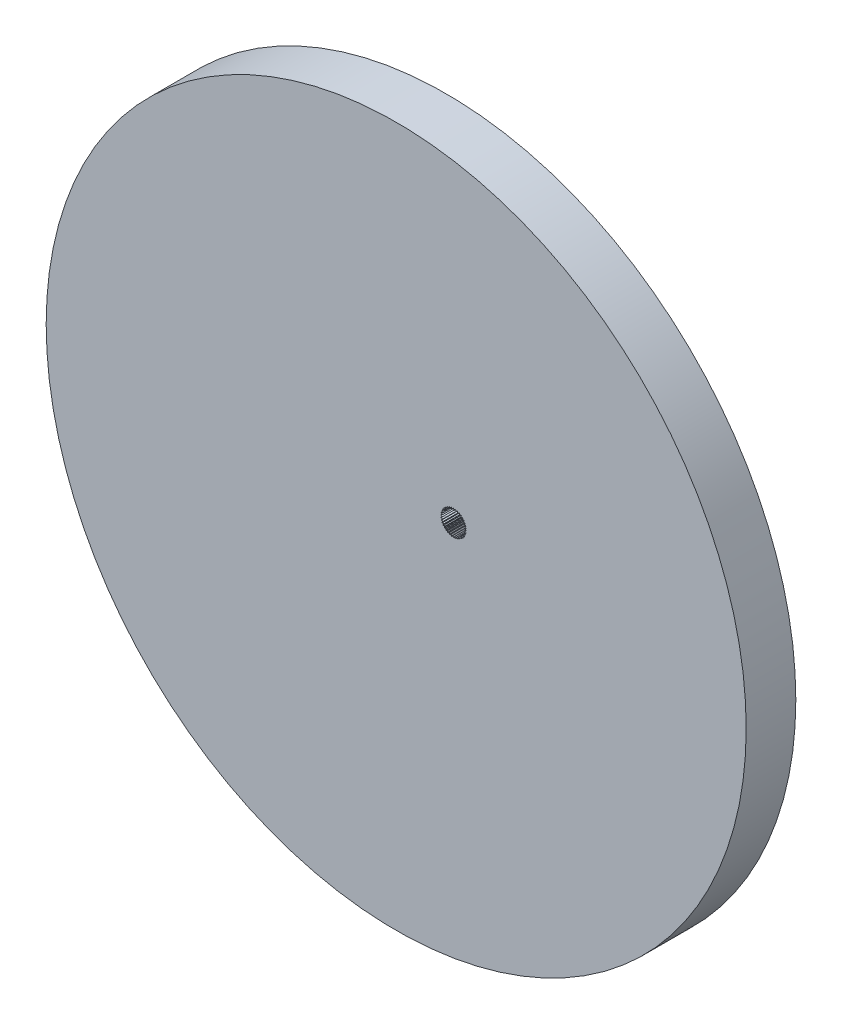
SolidWorks part; units mm, degrees
ref_plane "Front Plane" through (0, 0, 0) normal (0, 0, 1) x (1, 0, 0)
ref_plane "Top Plane" through (0, 0, 0) normal (0, 1, 0) x (1, 0, 0)
ref_plane "Right Plane" through (0, 0, 0) normal (1, 0, 0) x (0, 0, -1)
sketch "Sketch1" plane through (0, 0, 0) normal (0, 0, 1) x (1, 0, 0)
  circle A0 centre (0, 0) radius 70.548
extrude "Boss-Extrude1" add sketch "Sketch1" along normal blind 10
sketch "Sketch4" plane through (0, 0, 10) normal (0, 0, 1) x (1, 0, 0)
  line L0 (9.4595, 5.591) -> (9.128, 5.6333)
  line L1 (9.4595, 5.591) -> (9.2295, 5.361)
  line L2 (9.3572, 5.9482) -> (9.0925, 5.7592)
  line L3 (9.3572, 5.9482) -> (9.0371, 6.0445)
  line L4 (9.3151, 6.3174) -> (9.0229, 6.1746)
  line L5 (9.3151, 6.3174) -> (9.0152, 6.4651)
  line L6 (9.3343, 6.6885) -> (9.0226, 6.5957)
  line L7 (9.3343, 6.6885) -> (9.0628, 6.8836)
  line L8 (9.4144, 7.0514) -> (9.0916, 7.0112)
  line L9 (9.4144, 7.0514) -> (9.1787, 7.2885)
  line L10 (9.5531, 7.3962) -> (9.2281, 7.4096)
  line L11 (9.5531, 7.3962) -> (9.3596, 7.6688)
  line L12 (9.7466, 7.7134) -> (9.4282, 7.7802)
  line L13 (9.7466, 7.7134) -> (9.6007, 8.0142)
  line L14 (9.9897, 7.9945) -> (9.6867, 8.1127)
  line L15 (9.9897, 7.9945) -> (9.8953, 8.3151)
  line L16 (10.2758, 8.2317) -> (9.9963, 8.3982)
  line L17 (10.2758, 8.2317) -> (10.2354, 8.5635)
  line L18 (10.5969, 8.4186) -> (10.3487, 8.6288)
  line L19 (10.5969, 8.4186) -> (10.6117, 8.7525)
  line L20 (10.9445, 8.55) -> (10.7343, 8.7982)
  line L21 (10.9445, 8.55) -> (11.0141, 8.877)
  line L22 (11.309, 8.6225) -> (11.1425, 8.9019)
  line L23 (11.309, 8.6225) -> (11.4314, 8.9335)
  line L24 (11.6804, 8.634) -> (11.5622, 8.937)
  line L25 (11.6804, 8.634) -> (11.8524, 8.9206)
  line L26 (12.0487, 8.5842) -> (11.9819, 8.9025)
  line L27 (12.0487, 8.5842) -> (12.2655, 8.8386)
  line L28 (12.4037, 8.4744) -> (12.3903, 8.7994)
  line L29 (12.4037, 8.4744) -> (12.6594, 8.6897)
  line L30 (12.7358, 8.3078) -> (12.7761, 8.6305)
  line L31 (12.7358, 8.3078) -> (13.0235, 8.478)
  line L32 (13.036, 8.0887) -> (13.1288, 8.4004)
  line L33 (13.036, 8.0887) -> (13.3478, 8.2093)
  line L34 (13.296, 7.8232) -> (13.4389, 8.1154)
  line L35 (13.296, 7.8232) -> (13.6234, 7.8908)
  line L36 (13.5088, 7.5185) -> (13.6978, 7.7833)
  line L37 (13.5088, 7.5185) -> (13.8428, 7.5314)
  line L38 (13.6685, 7.183) -> (13.8985, 7.413)
  line L39 (13.6685, 7.183) -> (14.0001, 7.1407)
  line L40 (13.7708, 6.8258) -> (14.0355, 7.0148)
  line L41 (13.7708, 6.8258) -> (14.0909, 6.7294)
  line L42 (13.813, 6.4566) -> (14.1052, 6.5994)
  line L43 (13.813, 6.4566) -> (14.1128, 6.3089)
  line L44 (13.7937, 6.0854) -> (14.1055, 6.1783)
  line L45 (13.7937, 6.0854) -> (14.0652, 5.8904)
  line L46 (13.7137, 5.7226) -> (14.0364, 5.7628)
  line L47 (13.7137, 5.7226) -> (13.9494, 5.4855)
  line L48 (13.575, 5.3778) -> (13.9, 5.3644)
  line L49 (13.575, 5.3778) -> (13.7684, 5.1052)
  line L50 (13.3815, 5.0606) -> (13.6998, 4.9938)
  line L51 (13.3815, 5.0606) -> (13.5274, 4.7598)
  line L52 (13.1384, 4.7795) -> (13.4414, 4.6613)
  line L53 (13.1384, 4.7795) -> (13.2328, 4.4589)
  line L54 (12.8523, 4.5423) -> (13.1317, 4.3758)
  line L55 (12.8523, 4.5423) -> (12.8927, 4.2105)
  line L56 (12.5311, 4.3554) -> (12.7793, 4.1452)
  line L57 (12.5311, 4.3554) -> (12.5163, 4.0215)
  line L58 (12.1835, 4.224) -> (12.3938, 3.9758)
  line L59 (12.1835, 4.224) -> (12.114, 3.897)
  line L60 (11.8191, 4.1515) -> (11.9856, 3.8721)
  line L61 (11.8191, 4.1515) -> (11.6966, 3.8404)
  line L62 (11.4476, 4.14) -> (11.5659, 3.837)
  line L63 (11.4476, 4.14) -> (11.2757, 3.8534)
  line L64 (11.0794, 4.1898) -> (11.1461, 3.8715)
  line L65 (11.0794, 4.1898) -> (10.8626, 3.9354)
  line L66 (10.7243, 4.2995) -> (10.7378, 3.9746)
  line L67 (10.7243, 4.2995) -> (10.4686, 4.0843)
  line L68 (10.3922, 4.4662) -> (10.352, 4.1435)
  line L69 (10.3922, 4.4662) -> (10.1046, 4.296)
  line L70 (10.092, 4.6853) -> (9.9992, 4.3736)
  line L71 (10.092, 4.6853) -> (9.7803, 4.5647)
  line L72 (9.832, 4.9508) -> (9.6892, 4.6586)
  line L73 (9.832, 4.9508) -> (9.5047, 4.8831)
  line L74 (9.6193, 5.2555) -> (9.4303, 4.9907)
  line L75 (9.6193, 5.2555) -> (9.2852, 5.2426)
  circle A2 centre (11.564, 6.387) radius 2.55
  circle A3 centre (11.564, 6.387) radius 2.55
  point P123 (11.564, 6.387)
  dimension "D1" = 0.3
  dimension "D3" = 38
extrude "Cut-Extrude4" cut sketch "Sketch4" against normal blind 10 contours L42 A3 L41 L40 L39 L38 L37 L36 L35 L34 L33 L32 L31 L30 L29 L28 L27 L26 L25 L24 L23 L22 L21 L20 L19 L18 L17 L16 L15 L14 L13 L12 L11 L10 L9 region at (11.564, 6.387, 10)
